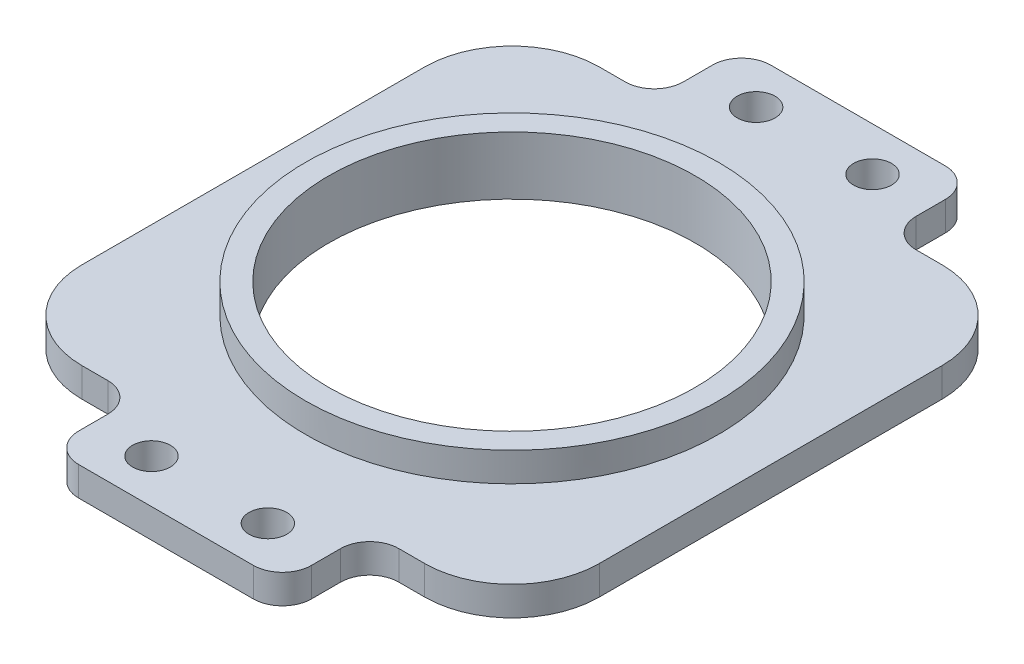
SolidWorks part; units mm, degrees
ref_plane "Front Plane" through (0, 0, 0) normal (0, 0, 1) x (1, 0, 0)
ref_plane "Top Plane" through (0, 0, 0) normal (0, 1, 0) x (1, 0, 0)
ref_plane "Right Plane" through (0, 0, 0) normal (1, 0, 0) x (0, 0, -1)
sketch "Sketch1" plane through (0, 0, 0) normal (0, 1, 0) x (1, 0, 0)
  line L1 (-44.45, -44.45) -> (44.45, -44.45)
  line L2 (-44.45, -44.45) -> (-44.45, 44.45)
  line L3 (-44.45, 44.45) -> (44.45, 44.45)
  line L4 (44.45, -44.45) -> (44.45, 44.45)
  line L5 (-44.45, -44.45) -> (44.45, 44.45) construction
  line L6 (-44.45, 44.45) -> (44.45, -44.45) construction
  point P0 (0, 0)
  dimension "D1" = 88.9
  dimension "D2" = 88.9
extrude "Boss-Extrude1" add sketch "Sketch1" along normal blind 5
sketch "Sketch2" plane through (0, 5, 0) normal (0, 1, 0) x (1, 0, 0)
  circle A0 centre (0, 0) radius 31.5
  circle A1 centre (0, 0) radius 35.5
extrude "Boss-Extrude2" add sketch "Sketch2" along normal blind 5
sketch "Sketch3" plane through (0, 0, 0) normal (0, -1, 0) x (1, 0, 0)
  line L0 (-44.45, 44.45) -> (44.45, 44.45) construction
  line L1 (0, 44.45) -> (20, 44.45)
  line L2 (0, 44.45) -> (0, 59.45)
  line L3 (0, 59.45) -> (20, 59.45)
  line L4 (20, 44.45) -> (20, 59.45)
  line L5 (44.45, -44.45) -> (-44.45, -44.45) construction
  line L6 (0, 44.45) -> (-20, 44.45)
  line L7 (0, 44.45) -> (0, 59.45)
  line L8 (0, 59.45) -> (-20, 59.45)
  line L9 (-20, 44.45) -> (-20, 59.45)
  line L10 (0, -44.45) -> (20, -44.45)
  line L11 (0, -44.45) -> (0, -59.45)
  line L12 (0, -59.45) -> (20, -59.45)
  line L13 (20, -44.45) -> (20, -59.45)
  line L15 (0, -44.45) -> (-20, -44.45)
  line L16 (0, -44.45) -> (0, -59.45)
  line L17 (0, -59.45) -> (-20, -59.45)
  line L18 (-20, -44.45) -> (-20, -59.45)
  line M9 (44.45, 44.45) -> (-44.45, 44.45)
  line M11 (-44.45, -44.45) -> (44.45, -44.45)
  dimension "D1" = 15
  dimension "D2" = 20
  dimension "D3" = 20
  dimension "D4" = 15
  dimension "D5" = 15
  dimension "D6" = 20
  dimension "D7" = 20
extrude "Boss-Extrude3" add sketch "Sketch3" against normal blind 5 contours L9 L2 L8 M9 | L4 L3 L2 M9 | L13 L11 L12 M11 | L18 L17 L11 M11 region at (10, 0, 51.95) region at (-10, 0, 51.95) region at (10, 0, -51.95) region at (-10, 0, -51.95)
sketch "Sketch4" plane through (0, 0, 0) normal (0, -1, 0) x (1, 0, 0)
  line L0 (-20, 44.45) -> (-20, 59.45) construction
  line L1 (20, 44.45) -> (20, 59.45) construction
  line L2 (20, 59.45) -> (-20, 59.45) construction
  circle A0 centre (10, 51.95) radius 3.25
  circle A1 centre (-10, 51.95) radius 3.25
  circle A2 centre (10, -51.95) radius 3.25
  circle A3 centre (-10, -51.95) radius 3.25
  dimension "D1" = 10
  dimension "D2" = 10
  dimension "D3" = 7.5
  dimension "D4" = 7.5
extrude "Cut-Extrude1" cut sketch "Sketch4" against normal blind 5
fillet "Fillet1" radius 15 4 edges at (-44.45, 2.5, 44.45) (44.45, 2.5, 44.45) (44.45, 2.5, -44.45) (-44.45, 2.5, -44.45)
fillet "Fillet2" radius 5 8 edges at (20, 2.5, -44.45) (20, 2.5, -59.45) (-20, 2.5, -59.45) (-20, 2.5, -44.45) (-20, 2.5, 44.45) (20, 2.5, 44.45) (-20, 2.5, 59.45) (20, 2.5, 59.45)
sketch "Sketch6" plane through (0, 5, 0) normal (0, 1, 0) x (1, 0, 0)
  circle A0 centre (0, 0) radius 31.5
extrude "Cut-Extrude2" cut sketch "Sketch6" against normal blind 5
